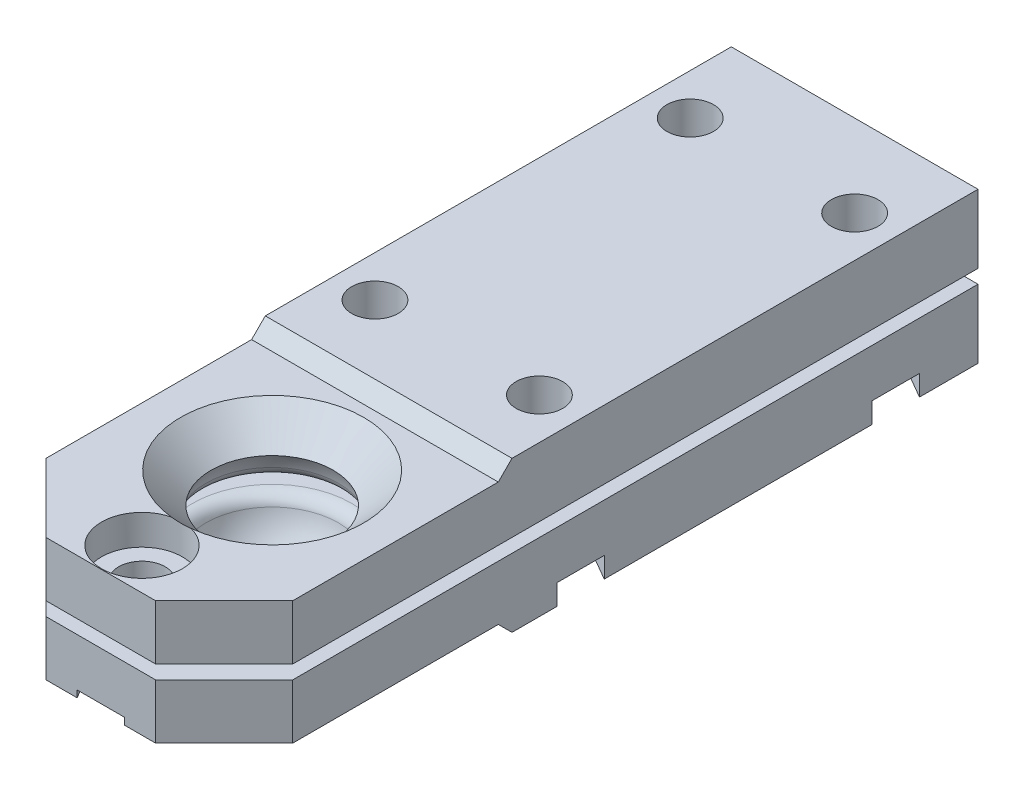
SolidWorks part; units mm, degrees
ref_plane "Front Plane" through (0, 0, 0) normal (0, 0, 1) x (1, 0, 0)
ref_plane "Top Plane" through (0, 0, 0) normal (0, 1, 0) x (1, 0, 0)
ref_plane "Right Plane" through (0, 0, 0) normal (1, 0, 0) x (0, 0, -1)
sketch "Sketch2" plane through (0, 0, 0) normal (0, 0, 1) x (1, 0, 0)
  line L1 (-9, -5.5) -> (9, -5.5)
  line L2 (-9, -5.5) -> (-9, 5.5)
  line L3 (-9, 5.5) -> (9, 5.5)
  line L4 (9, -5.5) -> (9, 5.5)
  line L5 (-9, -5.5) -> (9, 5.5) construction
  line L6 (-9, 5.5) -> (9, -5.5) construction
  point P0 (0, 0)
  dimension "D1" = 11
  dimension "D2" = 18
extrude "Boss-Extrude2" add sketch "Sketch2" along normal blind 55
sketch "Sketch3" plane through (0, 5.5, 0) normal (0, 1, 0) x (1, 0, 0)
  line L0 (9, -55) -> (9, 0) construction
  line L1 (-9, -55) -> (9, -55)
  line L2 (-9, -55) -> (-9, -35)
  line L3 (-9, -35) -> (9, -35)
  line L4 (9, -55) -> (9, -35)
  dimension "D1" = 20
extrude "Cut-Extrude1" cut sketch "Sketch3" against normal offset from surface (1 mm away) 1 up to face at (0, 5.5, 27.5)
chamfer "Chamfer5" distance 5 angle 45 2 edges at (-9, -0.5, 55) (9, -0.5, 55)
sketch "Sketch4" plane through (0, -5.5, 0) normal (0, -1, 0) x (1, 0, 0)
  line L0 (-9, 50) -> (-9, 0) construction
  line L1 (9, 55) -> (-9, 55)
  line L2 (9, 55) -> (9, 35)
  line L3 (9, 35) -> (-9, 35)
  line L4 (-9, 55) -> (-9, 35)
  line L6 (-4, 55) -> (4, 55) construction
  line L7 (9, 50) -> (9, 0) construction
  point P7 (0, 0)
  dimension "D1" = 20
extrude "Cut-Extrude2" cut sketch "Sketch4" against normal blind 1
sketch "Sketch5" plane through (0, 0, 0) normal (0, 0, -1) x (-1, 0, 0)
  circle A0 centre (0, 0) radius 3
  dimension "D1" = 6
extrude "Cut-Extrude3" cut sketch "Sketch5" against normal blind 30
sketch "Sketch7" plane through (0, 5.5, 0) normal (0, 1, 0) x (1, 0, 0)
  line L0 (9, -35) -> (9, 0) construction
  line L1 (9, 0) -> (-9, 0) construction
  line L2 (9, -35) -> (-9, -35) construction
  line L3 (-9, -35) -> (-9, 0) construction
  line L4 (-4, -55) -> (4, -55) construction
  circle A0 centre (6, -6) radius 1.7
  circle A1 centre (6, -29) radius 1.7
  circle A2 centre (-6, -29) radius 1.7
  circle A3 centre (-6, -6) radius 1.7
  circle A4 centre (0, -52) radius 1.7
  point P16 (0, 0)
  dimension "D1" = 3
  dimension "D6" = 3.4
  dimension "D10" = 3
  dimension "D2" = 6
  dimension "D3" = 6
  dimension "D4" = 6
  dimension "D5" = 3
  dimension "D7" = 3
  dimension "D8" = 3
  dimension "D9" = 6
extrude "Cut-Extrude5" cut sketch "Sketch7" against normal through all
sketch "Sketch6" plane through (0, 0, 0) normal (0, 0, -1) x (-1, 0, 0)
  line L0 (9, 5.5) -> (9, -5.5) construction
  line L1 (-9, -0.5) -> (9, -0.5)
  line L2 (-9, -0.5) -> (-9, 0.5)
  line L3 (-9, 0.5) -> (9, 0.5)
  line L4 (9, -0.5) -> (9, 0.5)
  line L5 (-9, -0.5) -> (9, 0.5) construction
  line L6 (-9, 0.5) -> (9, -0.5) construction
  point P0 (0, 0)
  dimension "D1" = 1
extrude "Cut-Extrude4" cut sketch "Sketch6" against normal through all
sketch "Sketch8" plane through (0, -5.5, 0) normal (0, -1, 0) x (1, 0, 0)
  line L1 (6, 25.5359) -> (9, 27.2679)
  line L2 (9, 27.2679) -> (9, 30.7321)
  line L3 (9, 30.7321) -> (6, 32.4641)
  line L4 (6, 32.4641) -> (3, 30.7321)
  line L5 (3, 30.7321) -> (3, 27.2679)
  line L6 (3, 27.2679) -> (6, 25.5359)
  line L7 (6, 2.5359) -> (9, 4.2679)
  line L8 (9, 4.2679) -> (9, 7.7321)
  line L9 (9, 7.7321) -> (6, 9.4641)
  line L10 (6, 9.4641) -> (3, 7.7321)
  line L11 (3, 7.7321) -> (3, 4.2679)
  line L12 (3, 4.2679) -> (6, 2.5359)
  line L13 (-6, 9.4641) -> (-9, 7.7321)
  line L14 (-9, 7.7321) -> (-9, 4.2679)
  line L15 (-9, 4.2679) -> (-6, 2.5359)
  line L16 (-6, 2.5359) -> (-3, 4.2679)
  line L17 (-3, 4.2679) -> (-3, 7.7321)
  line L18 (-3, 7.7321) -> (-6, 9.4641)
  line L19 (-6, 25.5359) -> (-3, 27.2679)
  line L20 (-3, 27.2679) -> (-3, 30.7321)
  line L21 (-3, 30.7321) -> (-6, 32.4641)
  line L22 (-6, 32.4641) -> (-9, 30.7321)
  line L23 (-9, 30.7321) -> (-9, 27.2679)
  line L24 (-9, 27.2679) -> (-6, 25.5359)
  circle A0 centre (6, 29) radius 3 construction
  circle A1 centre (6, 6) radius 3 construction
  circle A2 centre (-6, 6) radius 3 construction
  circle A3 centre (-6, 29) radius 3 construction
  dimension "D1" = 6
extrude "Cut-Extrude6" cut sketch "Sketch8" against normal blind 1.5
sketch "Sketch9" plane through (0, 0, 0) normal (0, 1, 0) x (1, 0, 0)
  line L0 (-5, -42.5) -> (5, -42.5)
  arc A0 (-5, -42.5) -> (5, -42.5) centre (0, -42.5) ccw
  point P3 (0, -42.5)
  point P4 (0, 0)
  point P6 (0, 0)
  point P9 (0, 0)
  dimension "D2" = 42.5
  dimension "D1" = 10
revolve "Cut-Revolve1" cut sketch "Sketch9" angle 360 about L0
chamfer "Chamfer2" distance 4.5 angle 45 1 edges at (0, 4.5, 40.3206) first distance on face at (0, 4.5, 40.3206)
chamfer "Chamfer3" distance 1 angle 45 1 edges at (0, 5.5, 35)
chamfer "Chamfer4" distance 1 angle 45 1 edges at (0, -5.5, 35)
sketch "Sketch10" plane through (0, 4.5, 0) normal (0, 1, 0) x (1, 0, 0)
  circle A0 centre (0, -52) radius 2.95
  dimension "D1" = 5.9
extrude "Cut-Extrude9" cut sketch "Sketch10" against normal blind 2.2
sketch "Sketch11" plane through (0, -4.5, 0) normal (0, -1, 0) x (1, 0, 0)
  line L1 (3.4641, 52) -> (1.7321, 55)
  line L2 (1.7321, 55) -> (-1.7321, 55)
  line L3 (-1.7321, 55) -> (-3.4641, 52)
  line L4 (-3.4641, 52) -> (-1.7321, 49)
  line L5 (-1.7321, 49) -> (1.7321, 49)
  line L6 (1.7321, 49) -> (3.4641, 52)
  circle A0 centre (0, 52) radius 3 construction
  dimension "D1" = 6
extrude "Cut-Extrude10" cut sketch "Sketch11" against normal blind 0.5
fillet "Fillet2" radius 1 1 edges at (0, 0.5, 47.4749)
fillet "Fillet3" radius 1 1 edges at (0, -0.5, 37.5251)
